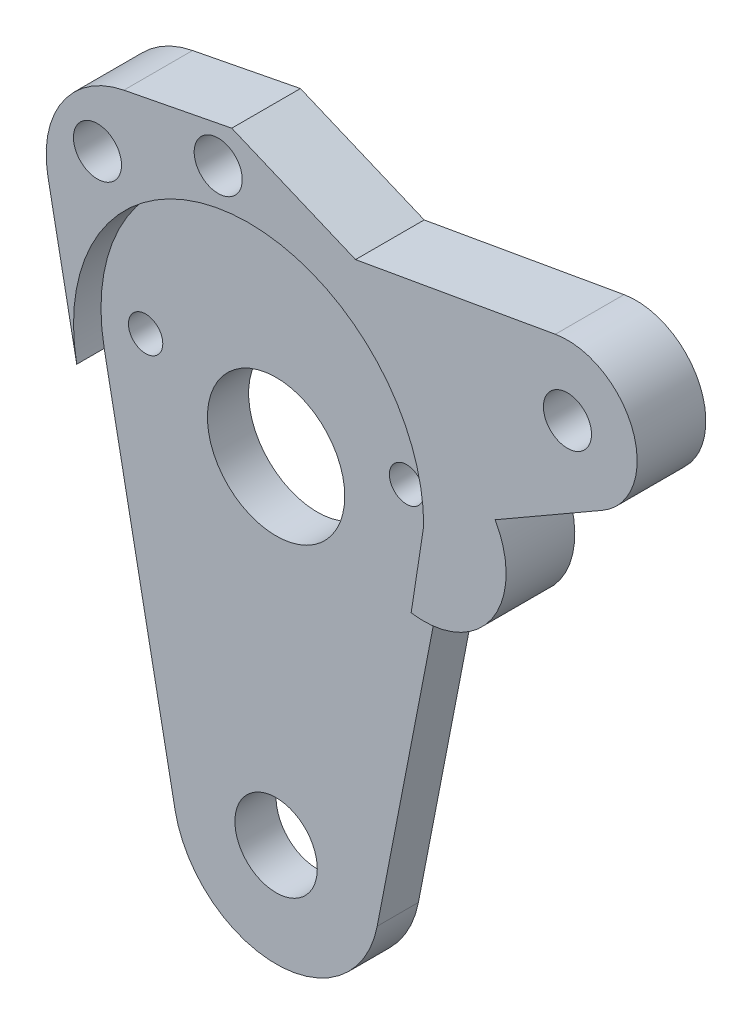
SolidWorks part; units mm, degrees
ref_plane "Front Plane" through (0, 0, 0) normal (0, 0, 1) x (1, 0, 0)
ref_plane "Top Plane" through (0, 0, 0) normal (0, 1, 0) x (1, 0, 0)
ref_plane "Right Plane" through (0, 0, 0) normal (1, 0, 0) x (0, 0, -1)
sketch "Sketch1" plane through (0, 0, 0) normal (0, 0, 1) x (1, 0, 0)
  line L0 (0, 0) -> (0, -27.5) construction
  line L1 (-7.3621, -28.9318) -> (-12.5155, -2.4341)
  line L2 (7.3621, -28.9318) -> (12.5155, -2.4341)
  line L3 (-9.5, 0) -> (9.5, 0) construction
  arc A0 (12.5155, -2.4341) -> (-12.5155, -2.4341) centre (0, 0) ccw
  arc A1 (-7.3621, -28.9318) -> (7.3621, -28.9318) centre (0, -27.5) ccw
  circle A2 centre (0, -27.5) radius 3
  circle A3 centre (0, -3) radius 5
  circle A4 centre (-9.5, 0) radius 1.25
  circle A5 centre (9.5, 0) radius 1.25
  dimension "D1" = 25.5
  dimension "D2" = 15
  dimension "D4" = 6
  dimension "D7" = 10
  dimension "D8" = 2.5
  dimension "D3" = 27.5
  dimension "D5" = 19
  dimension "D6" = 3
  dimension "D9" = 24.5
extrude "Boss-Extrude1" add sketch "Sketch1" along normal blind 3
sketch "Sketch2" plane through (0, 0, 0) normal (0, 0, 1) x (1, 0, 0)
  line L0 (-2.214, 12.5563) -> (22.3334, 16.8847)
  line L1 (0, 0) -> (12.75, 0) construction
  line L2 (25.7485, 7.4859) -> (12.75, 0)
  arc A0 (12.5155, -2.4341) -> (-12.5155, -2.4341) centre (0, 0) ccw construction
  arc A1 (12.75, 0) -> (-2.214, 12.5563) centre (0, 0) ccw
  arc A2 (22.3334, 16.8847) -> (25.7485, 7.4859) centre (23.215, 11.8852) cw
  circle A4 centre (23.215, 11.8852) radius 1.75
  dimension "D4" = 3.5
  dimension "D1" = 10
  dimension "D2" = 10
  dimension "D3" = 15
extrude "Boss-Extrude2" add sketch "Sketch2" along normal blind 5
sketch "Sketch4" plane through (0, 0, 0) normal (0, 0, 1) x (1, 0, 0)
  line L0 (-12.5155, -2.4341) -> (-14.6155, 8.3636)
  line L1 (-9.0806, 16.5712) -> (-1.2277, 18.0985)
  line L2 (-1.2277, 18.0985) -> (7.786, 14.3196)
  line L3 (22.3334, 16.8847) -> (-2.214, 12.5563) construction
  line L5 (7.786, 14.3196) -> (-2.214, 12.5563)
  line L6 (-12.5155, -2.4341) -> (-7.3621, -28.9318) construction
  arc A0 (-2.214, 12.5563) -> (-12.5155, -2.4341) centre (0, 0) ccw construction
  arc A2 (-2.214, 12.5563) -> (-12.5155, -2.4341) centre (0, 0) ccw
  arc A3 (-14.6155, 8.3636) -> (-9.0806, 16.5712) centre (-7.7442, 9.7) cw
  circle A4 centre (-11.0059, 11.7506) radius 1.75
  circle A5 centre (-2.214, 15.2348) radius 1.75
  point P19 (-15.9519, 15.2348)
  point P22 (-11.0059, 11.7506)
  point P23 (-2.214, 15.2348)
  dimension "D1" = 15
  dimension "D3" = 10
  dimension "D4" = 7
  dimension "D5" = 3.5
  dimension "D2" = 18
extrude "Boss-Extrude3" add sketch "Sketch4" along normal blind 5
sketch "Sketch5" plane through (0, 0, 0) normal (0, 0, 1) x (1, 0, 0)
  line L0 (12.75, 0) -> (25.7485, 7.4859) construction
  line L1 (7.3621, -28.9318) -> (12.5155, -2.4341) construction
  line L2 (12.75, 0) -> (11.8356, -5.9299)
  line L3 (12.75, 0) -> (17.9494, 2.9944)
  arc A0 (17.9494, 2.9944) -> (11.8356, -5.9299) centre (12.75, 0) cw
  dimension "D1" = 6
extrude "Boss-Extrude4" add sketch "Sketch5" along normal blind 5
